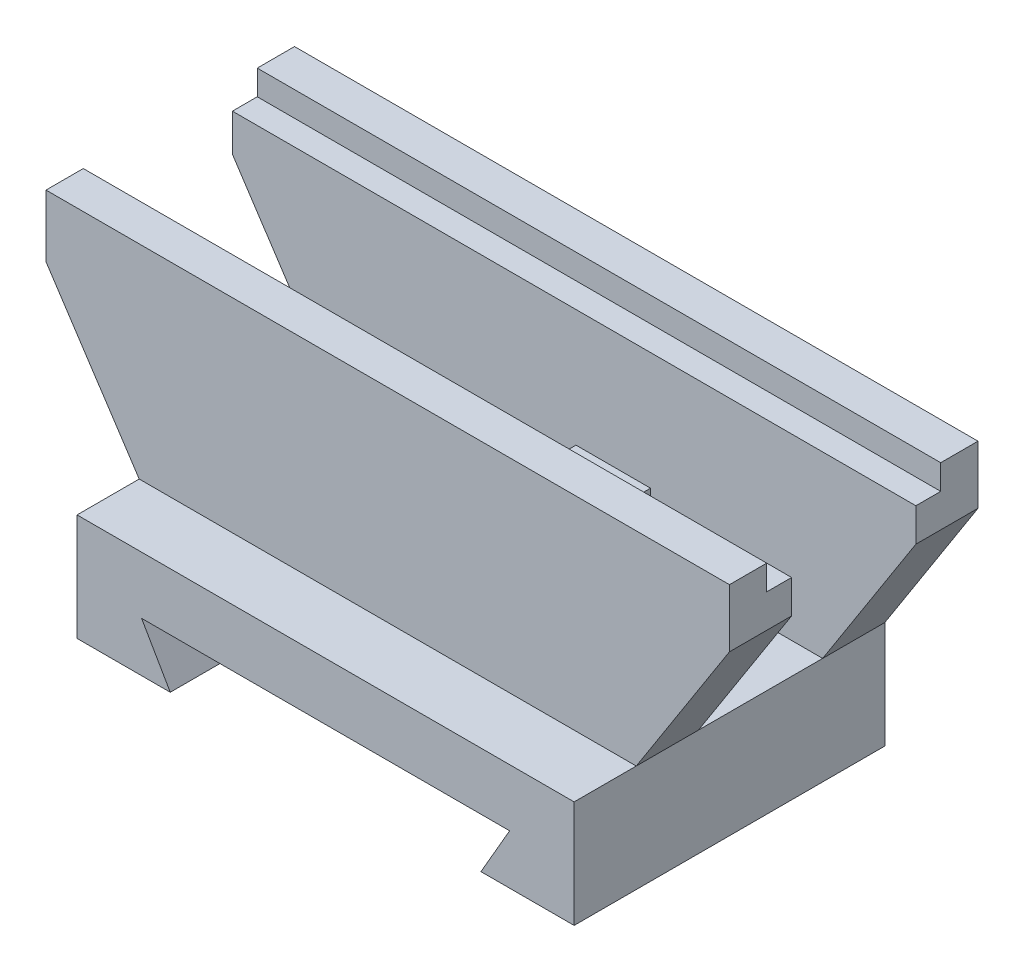
SolidWorks part; units mm, degrees
material "Cast Alloy Steel"
ref_plane "Front Plane" through (0, 0, 0) normal (0, 0, 1) x (1, 0, 0)
ref_plane "Top Plane" through (0, 0, 0) normal (0, 1, 0) x (1, 0, 0)
ref_plane "Right Plane" through (0, 0, 0) normal (1, 0, 0) x (0, 0, -1)
sketch "Sketch1" plane through (0, 0, 0) normal (0, 0, 1) x (1, 0, 0)
  line L0 (69.6188, 8) -> (65, 0)
  line L2 (0, 0) -> (0, 17.2208)
  line L3 (0, 17.2208) -> (80, 17.2208)
  line L4 (80, 0) -> (80, 17.2208)
  line L7 (10.3812, 8) -> (69.6188, 8)
  line L9 (10.3812, 8) -> (15, 0)
  line L13 (65, 0) -> (80, 0)
  line L14 (0, 0) -> (15, 0)
  dimension "D1" = 80
  dimension "D3" = 50
  dimension "D6" = 15
extrude "Boss-Extrude1" add sketch "Sketch1" along normal blind 50 contours L3 L4 L13 L0 L7 L9 L14 L2
sketch "Sketch2" plane through (0, 0, 0) normal (0, 0, 1) x (1, 0, 0)
  line L0 (65, 0) -> (80, 0) construction
  line L1 (0, 17.2208) -> (80, 17.2208)
  line L2 (-15, 39.9991) -> (-15, 50)
  line L3 (-15, 50) -> (95, 50)
  line L4 (95, 40.6394) -> (95, 50)
  line L5 (0, 17.2208) -> (80, 17.2208) construction
  line L6 (80, 17.2208) -> (95, 40.6394)
  line L7 (0, 17.2208) -> (-15, 39.9991)
  point P14 (-14.463, 40.3307)
  dimension "D1" = 50
  dimension "D3" = 15
extrude "Boss-Extrude2" add sketch "Sketch2" along normal blind 10 contours L6 L4 L3 L2 L7 L1
extrude "Boss-Extrude3" add sketch "Sketch2<3>" along normal blind 10 from offset 30
sketch "Sketch2<3>" plane through (0, 0, 0) normal (0, 0, 1) x (1, 0, 0) same geometry as "Sketch2"
sketch "Sketch3" plane through (0, 17.2208, 0) normal (0, 1, 0) x (1, 0, 0)
  line L1 (45.4199, -25.1262) -> (57.4199, -25.1262)
  line L2 (45.4199, -25.1262) -> (45.4199, -15.1262)
  line L3 (45.4199, -15.1262) -> (57.4199, -15.1262)
  line L4 (57.4199, -25.1262) -> (57.4199, -15.1262)
  line L5 (45.4199, -25.1262) -> (57.4199, -15.1262) construction
  line L6 (45.4199, -15.1262) -> (57.4199, -25.1262) construction
  point P0 (51.4199, -20.1262)
  dimension "D1" = 10
  dimension "D2" = 12
extrude "Boss-Extrude4" add sketch "Sketch3" along normal blind 15 contours L4 L3 L2 L1
sketch "Sketch4" plane through (0, 0, 0) normal (1, 0, 0) x (0, 0, -1)
  line L0 (-40, 50) -> (-30, 50) construction
  line L1 (-34, 50) -> (-6, 50)
  line L2 (-34, 50) -> (-34, 46)
  line L3 (-34, 46) -> (-6, 46)
  line L4 (-6, 50) -> (-6, 46)
  line L5 (-10, 40.6394) -> (-10, 50) construction
  line L7 (-25.1262, 32.2208) -> (-15.1262, 32.2208) construction
  circle A0 centre (-20.1262, 25.2208) radius 3
  dimension "D5" = 6
  dimension "D1" = 28
  dimension "D2" = 4
  dimension "D3" = 4
  dimension "D4" = 7
extrude "Cut-Extrude1" cut sketch "Sketch4" against normal through all both and the other way through all
